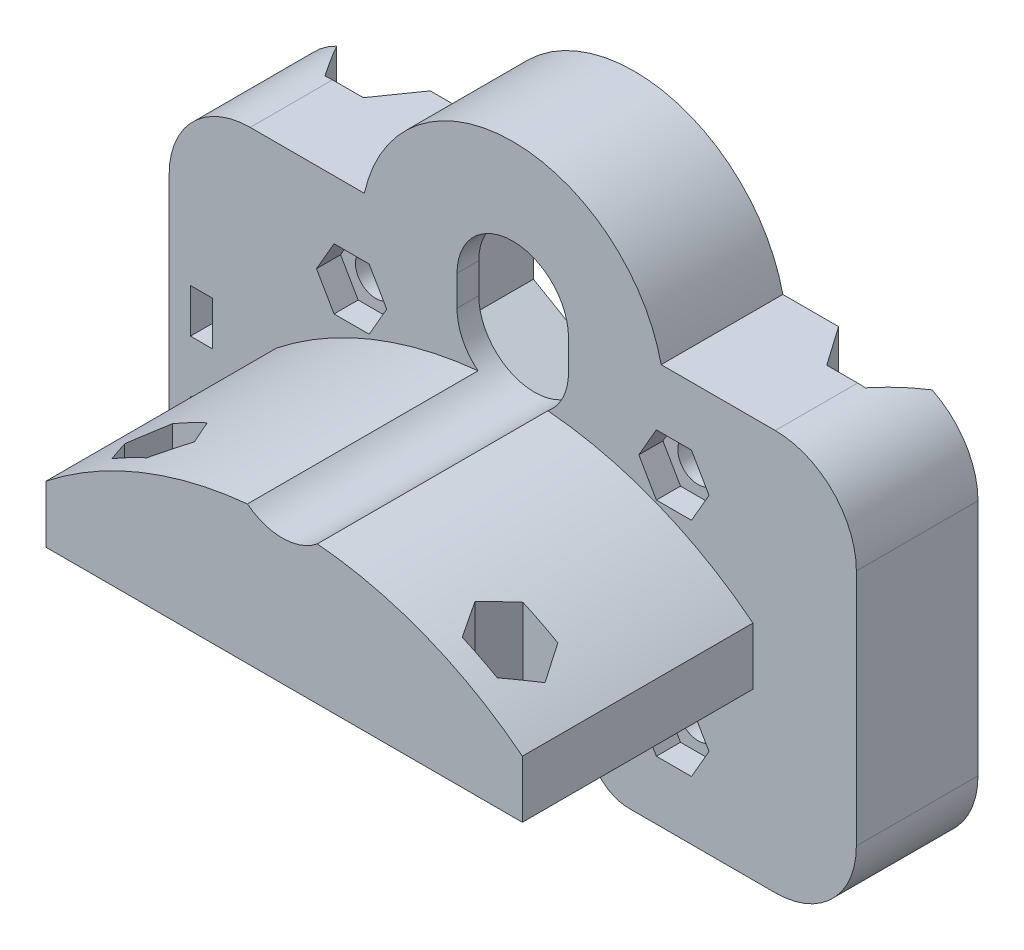
SolidWorks part; units mm, degrees
note: The reader was unsure of these and kept them because the rebuilt part matched: shared geometry of "Sketch11<4>".
material "ABS"
ref_plane "Front Plane" through (0, 0, 0) normal (0, 0, 1) x (1, 0, 0)
ref_plane "Top Plane" through (0, 0, 0) normal (0, 1, 0) x (1, 0, 0)
ref_plane "Right Plane" through (0, 0, 0) normal (1, 0, 0) x (0, 0, -1)
sketch "Sketch1" plane through (0, 0, 0) normal (0, 0, 1) x (1, 0, 0)
  line L0 (0, 41.9085) -> (0, -42.5521) construction
  line L1 (-25.9, -19.75) -> (-11.5, -19.75)
  line L2 (-33.9, -11.75) -> (-33.9, 11.75)
  line L3 (-25.9, 19.75) -> (-14.6437, 19.75)
  line L4 (33.9, -11.75) -> (33.9, 11.75)
  line L5 (-33.9, -19.75) -> (-30.8948, -17.9992) construction
  line L6 (-33.9, 19.75) -> (-28.3215, 16.5) construction
  line L7 (-42.6135, 0) -> (44.2952, 0) construction
  line L8 (7.5, -13) -> (7.5, -15.75)
  line L9 (-7.5, -13) -> (-7.5, -15.75)
  line L10 (11.5, -19.75) -> (25.9, -19.75)
  line L11 (-40.2297, 16.5) -> (44.2952, 16.5) construction
  line L12 (-3.1481, 1.8341) -> (0, 0) construction
  line L13 (28.3215, 16.5) -> (33.9, 19.75) construction
  line L14 (14.6437, 19.75) -> (25.9, 19.75)
  line L15 (0, 0) -> (3.1481, 1.8341) construction
  line L16 (30.8948, -17.9992) -> (33.9, -19.75) construction
  arc A0 (25.9, 19.75) -> (33.9, 11.75) centre (25.9, 11.75) cw
  arc A1 (33.9, -11.75) -> (25.9, -19.75) centre (25.9, -11.75) cw
  arc A2 (-25.9, -19.75) -> (-33.9, -11.75) centre (-25.9, -11.75) cw
  arc A3 (-33.9, 11.75) -> (-25.9, 19.75) centre (-25.9, 11.75) cw
  arc A4 (7.5, -13) -> (-7.5, -13) centre (0, -13) ccw
  arc A5 (-7.5, -15.75) -> (-11.5, -19.75) centre (-11.5, -15.75) cw
  arc A6 (7.5, -15.75) -> (11.5, -19.75) centre (11.5, -15.75) ccw
  circle A7 centre (-15.9, 10.9447) radius 2
  arc A8 (14.6437, 19.75) -> (-14.6437, 19.75) centre (0, 16.5) ccw
  circle A9 centre (-15.9, -10.9447) radius 2
  circle A10 centre (15.9, -10.9447) radius 2
  circle A11 centre (15.9, 10.9447) radius 2
  point P0 (0, 0)
  dimension "D3" = 8
  dimension "D4" = 15
  dimension "D6" = 4
  dimension "D7" = 4
  dimension "D9" = 15
  dimension "D10" = 4
  dimension "D1" = 67.8
  dimension "D2" = 39.5
  dimension "D5" = 6.75
  dimension "D8" = 3.25
  dimension "D11" = 8.8053
  dimension "D12" = 18
extrude "Boss-Extrude4" add sketch "Sketch1" along normal blind 34.75
sketch "Sketch5" plane through (0, 0, 34.75) normal (0, 0, 1) x (1, 0, 0)
  line L0 (-23.3, -3.45) -> (-23.3, 2.2)
  line L1 (23.7, 2.2005) -> (23.7, -3.45)
  line L2 (23.7, -3.45) -> (-23.3, -3.45)
  line L3 (-33.9, 11.75) -> (-33.9, -11.75) construction
  line L4 (-25.9, -19.75) -> (-11.5, -19.75) construction
  arc A0 (-23.3, 2.2) -> (23.7, 2.2005) centre (0.2003, -27.5422) cw
  arc M4 (33.9, 11.75) -> (25.9, 19.75) centre (25.9, 11.75) ccw
  line M5 (25.9, 19.75) -> (14.6437, 19.75)
  arc M6 (14.6437, 19.75) -> (-14.6437, 19.75) centre (0, 16.5) ccw
  line M7 (-14.6437, 19.75) -> (-25.9, 19.75)
  arc M8 (-25.9, 19.75) -> (-33.9, 11.75) centre (-25.9, 11.75) ccw
  line M9 (-33.9, 11.75) -> (-33.9, -11.75)
  arc M10 (-33.9, -11.75) -> (-25.9, -19.75) centre (-25.9, -11.75) ccw
  line M11 (-25.9, -19.75) -> (-11.5, -19.75)
  arc M12 (-11.5, -19.75) -> (-7.5, -15.75) centre (-11.5, -15.75) ccw
  line M13 (-7.5, -15.75) -> (-7.5, -13)
  arc M14 (-7.5, -13) -> (7.5, -13) centre (0, -13) cw
  line M15 (7.5, -13) -> (7.5, -15.75)
  arc M16 (7.5, -15.75) -> (11.5, -19.75) centre (11.5, -15.75) ccw
  line M17 (11.5, -19.75) -> (25.9, -19.75)
  arc M18 (25.9, -19.75) -> (33.9, -11.75) centre (25.9, -11.75) ccw
  line M19 (33.9, -11.75) -> (33.9, 11.75)
  circle M20 centre (-15.9, 10.9447) radius 2
  dimension "D1" = 37.906
  dimension "D2" = 5.65
  dimension "D3" = 47
  dimension "D4" = 5.6505
  dimension "D5" = 10.6
  dimension "D6" = 16.3
extrude "Cut-Extrude2" cut sketch "Sketch5" against normal blind 22.75 contours L0 A0 L1 L2 M19 M4 M5 M6 M7 M8 M9 M10 M11 M12 M13 M14 M15 M16 M17 M18 M20
sketch "Sketch6" plane through (0, 0, 34.75) normal (0, 0, 1) x (1, 0, 0)
  line L0 (-5.5, 14.4931) -> (-5.5, 17.4898)
  line L1 (5.5, 17.4898) -> (5.5, 14.4931)
  line L3 (-23.3, -3.45) -> (-23.3, 2.2) construction
  arc A0 (5.5, 17.4898) -> (-5.5, 17.4898) centre (0, 17.4898) ccw
  arc A1 (-5.5, 14.4931) -> (5.5, 14.4931) centre (0, 14.4931) ccw
  circle A2 centre (0, 16.5) radius 14.9899 construction
  arc A4 (14.6437, 19.75) -> (-14.6437, 19.75) centre (0, 16.5) ccw construction
  dimension "D1" = 0.9898
  dimension "D4" = 5.5
  dimension "D2" = 2.0069
  dimension "D3" = 29.9798
  dimension "D9" = 0.0005
extrude "Cut-Extrude3" cut sketch "Sketch6" against normal up to next
sketch "Sketch7" plane through (0, 0, 12) normal (0, 0, 1) x (1, 0, 0)
  line L0 (0, 35.1713) -> (0, -22.6934) construction
  line L1 (-41.6403, 0) -> (40.1344, 0) construction
sketch "Sketch9" plane through (0, 19.75, 0) normal (0, 1, 0) x (1, 0, 0)
  line L0 (-29.3668, 0) -> (-26.65, -3.88)
  line L1 (-26.65, -3.88) -> (-22.86, -3.88)
  line L2 (-22.86, -3.88) -> (-20.1432, 0)
  line L3 (-20.1432, 0) -> (-29.3668, 0)
  line L4 (-33.9, 0) -> (-33.9, -12) construction
  line L5 (0, 7.9559) -> (0, -40.3734) construction
  line L6 (22.86, -3.88) -> (20.1432, 0)
  line L7 (20.1432, 0) -> (29.3668, 0)
  line L8 (29.3668, 0) -> (26.65, -3.88)
  line L9 (26.65, -3.88) -> (22.86, -3.88)
  line L10 (-14.6437, 0) -> (-25.9, 0) construction
  dimension "D1" = 7.25
  dimension "D2" = 3.79
  dimension "D3" = 3.88
  dimension "D4" = 125
  dimension "D5" = 125
extrude "Cut-Extrude4" cut sketch "Sketch9" against normal through all
sketch "Sketch10" plane through (0, -3.45, 0) normal (0, -1, 0) x (1, 0, 0)
  line L0 (0, 40.7466) -> (0, -14.3002) construction
  line L1 (23.7, 34.75) -> (-23.3, 34.75) construction
  line L2 (-23.3, 12) -> (-23.3, 34.75) construction
  circle A0 centre (-17.3, 29.5) radius 1.8
  circle A1 centre (17.3, 29.5) radius 1.8
  dimension "D1" = 5.25
  dimension "D3" = 3.6
  dimension "D2" = 6
extrude "Cut-Extrude5" cut sketch "Sketch10" against normal up to next
ref_plane "Plane1" through (-0.0486, 10.2061, 0) normal (0.0048, -1, 0) x (-1, -0.0048, 0)
sketch "Sketch11" plane through (-0.0486, 10.2061, 0) normal (0.0048, -1, 0) x (-1, -0.0048, 0)
  line L0 (-23.6833, -34.75) -> (23.3162, -34.75) construction
  line L1 (19.0425, -32.49) -> (20.7688, -29.5)
  line L2 (20.7688, -29.5) -> (19.0425, -26.51)
  line L3 (19.0425, -26.51) -> (15.59, -26.51)
  line L4 (15.59, -26.51) -> (13.8637, -29.5)
  line L5 (13.8637, -29.5) -> (15.59, -32.49)
  line L6 (15.59, -32.49) -> (19.0425, -32.49)
  line L7 (-23.7102, -34.75) -> (-3.5149, -34.75) construction
  line L8 (-19.0096, -26.51) -> (-20.7359, -29.5)
  line L9 (-20.7359, -29.5) -> (-19.0096, -32.49)
  line L10 (-19.0096, -32.49) -> (-15.5571, -32.49)
  line L11 (-15.5571, -32.49) -> (-13.8308, -29.5)
  line L12 (-13.8308, -29.5) -> (-15.5571, -26.51)
  line L13 (-15.5571, -26.51) -> (-19.0096, -26.51)
  circle A0 centre (17.3162, -29.5) radius 2.99 construction
  circle A1 centre (-17.2834, -29.5) radius 2.99 construction
  ellipse E0 centre (17.3162, -29.5) end of major axis (17.3162, -31.3) minor radius 1.8 construction
  ellipse E1 centre (-17.2834, -29.5) end of major axis (-17.2834, -31.3) minor radius 1.8 construction
  ellipse E2 centre (17.3162, -29.5) end of major axis (17.3162, -31.3) minor radius 1.8
  ellipse E3 centre (-17.2834, -29.5) end of major axis (-17.2834, -31.3) minor radius 1.8
  dimension "D1" = 5.98
  dimension "D2" = 5.98
extrude "Cut-Extrude6" cut sketch "Sketch11" along normal offset from surface (11.2319 mm away) 2.35 contours E2 | L5 L6 L1 L2 L3 L4 E2
sketch "Sketch12" plane through (0, -3.45, 0) normal (0, -1, 0) x (-1, 0, 0)
  line L0 (0, 11.1477) -> (0, -60.5065) construction
extrude "Cut-Extrude7" cut sketch "Sketch11<4>" along direction (0, 1, 0) on the side of the normal offset from surface (11.3802 mm away) 2.35 contours E3 | L12 L13 L8 L9 L10 L11 E3
sketch "Sketch11<4>" plane through (-0.0486, 10.2061, 0) normal (0.0048, -1, 0) x (-1, -0.0048, 0) same geometry as "Sketch11"
sketch "Sketch14" plane through (0, 0, 0) normal (0, 0, -1) x (-1, 0, 0)
  line L0 (0, 44.0291) -> (0, -26.022) construction
  line L1 (0, 41.9085) -> (0, -42.5521) construction
  line L3 (0, 3) -> (9.9593, 8.75)
  line L4 (9.9593, 8.75) -> (9.9593, 23.25)
  line L5 (0, 29) -> (9.9593, 23.25)
  line L6 (0, 29) -> (-9.9593, 23.25)
  line L7 (-9.9593, 23.25) -> (-9.9593, 8.75)
  line L8 (-9.9593, 8.75) -> (0, 3)
  line L9 (-20.1432, 19.75) -> (-14.6437, 19.75) construction
  arc A0 (7.5, -13) -> (-7.5, -13) centre (0, -13) ccw construction
  arc A1 (7.5, -13) -> (-7.5, -13) centre (0, -13) ccw
  dimension "D1" = 11.5
  dimension "D2" = 14.5
  dimension "D3" = 60
  dimension "D4" = 11.5
  dimension "D6" = 16.75
extrude "Cut-Extrude8" cut sketch "Sketch14" against normal blind 9.85 contours L0 L6 L7 L8 L3 | L6 L0 L3 L4 L5
sketch "Sketch15" plane through (0, 0, 12) normal (0, 0, 1) x (1, 0, 0)
  line L0 (-14.6437, 19.75) -> (-25.9, 19.75) construction
  line L1 (-14.1679, 13.9447) -> (-17.6321, 13.9447)
  line L2 (-17.6321, 13.9447) -> (-19.3641, 10.9447)
  line L3 (-19.3641, 10.9447) -> (-17.6321, 7.9447)
  line L4 (-17.6321, 7.9447) -> (-14.1679, 7.9447)
  line L5 (-14.1679, 7.9447) -> (-12.4359, 10.9447)
  line L6 (-12.4359, 10.9447) -> (-14.1679, 13.9447)
  line L7 (0, -17.7367) -> (0, 43.9408) construction
  line L8 (-47.3402, 0) -> (50.132, 0) construction
  line L9 (-14.1679, -13.9447) -> (-17.6321, -13.9447)
  line L10 (-12.4359, -10.9447) -> (-14.1679, -13.9447)
  line L11 (-14.1679, -7.9447) -> (-12.4359, -10.9447)
  line L12 (-17.6321, -7.9447) -> (-14.1679, -7.9447)
  line L13 (-19.3641, -10.9447) -> (-17.6321, -7.9447)
  line L14 (-17.6321, -13.9447) -> (-19.3641, -10.9447)
  line L15 (12.4359, -10.9447) -> (14.1679, -13.9447)
  line L16 (14.1679, -7.9447) -> (12.4359, -10.9447)
  line L17 (17.6321, -7.9447) -> (14.1679, -7.9447)
  line L18 (19.3641, -10.9447) -> (17.6321, -7.9447)
  line L19 (17.6321, -13.9447) -> (19.3641, -10.9447)
  line L20 (14.1679, -13.9447) -> (17.6321, -13.9447)
  line L21 (17.6321, 13.9447) -> (19.3641, 10.9447)
  line L22 (19.3641, 10.9447) -> (17.6321, 7.9447)
  line L23 (17.6321, 7.9447) -> (14.1679, 7.9447)
  line L24 (14.1679, 7.9447) -> (12.4359, 10.9447)
  line L25 (12.4359, 10.9447) -> (14.1679, 13.9447)
  line L26 (14.1679, 13.9447) -> (17.6321, 13.9447)
  circle A0 centre (-15.9, 10.9447) radius 3 construction
  circle M26 centre (-15.9, 10.9447) radius 2
  circle M27 centre (15.9, -10.9447) radius 2
  circle M28 centre (15.9, 10.9447) radius 2
  circle M29 centre (-15.9, -10.9447) radius 2
  dimension "D1" = 6
extrude "Cut-Extrude9" cut sketch "Sketch15" against normal blind 2.38 contours M26 | L5 L6 L1 L2 L3 L4 M26 | M28 | L26 L25 L24 L23 L22 L21 M28 | M27 | L15 L20 L19 L18 L17 L16 M27 | M29 | L14 L9 L10 L11 L12 L13 M29
sketch "Sketch16" plane through (-33.9, 0, 0) normal (-1, 0, 0) x (0, 0, 1)
  line L0 (12, -19.75) -> (12, -11.75) construction
  line L1 (3.88, -19.75) -> (0, -19.75) construction
  line L2 (12, -19.75) -> (3.88, -19.75) construction
  line L3 (0, -11.75) -> (0, -18.9598) construction
  line L4 (0, 11.75) -> (0, -11.75) construction
  line L5 (12, -11.75) -> (0, -11.75) construction
  line L6 (12, 11.75) -> (12, -11.75) construction
  line L7 (12, 11.75) -> (0, 11.75) construction
  line L8 (12, 19.75) -> (0, 19.75) construction
  line L9 (12, -19.75) -> (12, -11.75)
  line L10 (3.88, -19.75) -> (0, -19.75)
  line L11 (12, -19.75) -> (3.88, -19.75)
  line L12 (0, -11.75) -> (0, -18.9598)
  line L13 (0, 11.75) -> (0, -11.75)
  line L14 (12, -11.75) -> (0, -11.75)
  line L15 (12, 11.75) -> (12, -11.75)
  line L16 (12, 11.75) -> (0, 11.75)
  line L17 (12, 19.75) -> (0, 19.75)
  circle A0 centre (8.05, -8.33) radius 1.25
  circle A1 centre (8.05, 1.13) radius 1.25
  dimension "D1" = 2.5
  dimension "D3" = 3.95
  dimension "D2" = 11.42
  dimension "D4" = 9.46
  dimension "D5" = 3.95
extrude "Cut-Extrude10" cut sketch "Sketch16" against normal blind 6.1 contours A1 | A0
sketch "Sketch17" plane through (0, 0, 12) normal (0, 0, 1) x (1, 0, 0)
  line L0 (-33.9, 11.75) -> (-33.9, -11.75) construction
  line L1 (-31.8, -1.035) -> (-29.6, -1.035)
  line L2 (-31.8, -1.035) -> (-31.8, 3.295)
  line L3 (-31.8, 3.295) -> (-29.6, 3.295)
  line L4 (-29.6, -1.035) -> (-29.6, 3.295)
  line L5 (-31.8, -6.165) -> (-29.6, -6.165)
  line L6 (-31.8, -6.165) -> (-31.8, -10.495)
  line L7 (-31.8, -10.495) -> (-29.6, -10.495)
  line L8 (-29.6, -6.165) -> (-29.6, -10.495)
  line L9 (-25.9, -19.75) -> (-11.5, -19.75) construction
  dimension "D1" = 2.1
  dimension "D2" = 9.255
  dimension "D3" = 4.33
  dimension "D4" = 2.2
  dimension "D5" = 5.13
  dimension "D6" = 4.33
  dimension "D7" = 2.2
extrude "Cut-Extrude11" cut sketch "Sketch17" against normal blind 6.55
sketch "Sketch18" plane through (-29.6, 0, 0) normal (-1, 0, 0) x (0, 0, 1)
  line L0 (6.7, -1.035) -> (5.45, 1.13)
  line L1 (5.45, -1.035) -> (12, -1.035) construction
  line L2 (5.45, -1.035) -> (5.45, 3.295) construction
  line L3 (5.45, 1.13) -> (6.7, 3.295)
  line L4 (5.45, 3.295) -> (12, 3.295) construction
  line L5 (6.7, 3.295) -> (5.45, 3.295)
  line L6 (5.45, 3.295) -> (5.45, -1.035)
  line L7 (5.45, -1.035) -> (6.7, -1.035)
  line L8 (6.7, -1.035) -> (6.678, -1.0465)
  line L9 (12, 1.13) -> (12, -8.33) construction
  line L10 (12, -1.035) -> (12, 3.295) construction
  line L11 (12, -10.495) -> (12, -6.165) construction
  line L12 (12, -3.6) -> (2.6249, -3.6) construction
  line M3 (12, 3.295) -> (5.45, 3.295)
  line M4 (5.45, 3.295) -> (5.45, -1.035)
  line M5 (5.45, -1.035) -> (12, -1.035)
  dimension "D1" = 120
extrude "Boss-Extrude5" add sketch "Sketch18" along normal blind 2.2 contours L3 M4 M3 | L0 M5 M4
sketch "Sketch21" plane through (-31.8, 0, 0) normal (1, 0, 0) x (0, 0, -1)
  line L0 (-6.7, -6.165) -> (-5.45, -8.33)
  line L1 (-5.45, -6.165) -> (-12, -6.165) construction
  line L2 (-5.45, -6.165) -> (-5.45, -10.495) construction
  line L3 (-5.45, -8.33) -> (-6.7, -10.495)
  line L4 (-5.45, -10.495) -> (-12, -10.495) construction
  line L5 (-6.7, -10.495) -> (-5.45, -10.495)
  line L6 (-5.45, -10.495) -> (-5.45, -6.165)
  line L7 (-5.45, -6.165) -> (-6.7, -6.165)
  line M4 (-12, -10.495) -> (-5.45, -10.495)
  line M5 (-5.45, -10.495) -> (-5.45, -6.165)
  line M6 (-5.45, -6.165) -> (-12, -6.165)
  dimension "D1" = 120
  dimension "D2" = 120
extrude "Boss-Extrude6" add sketch "Sketch21" along normal blind 2.2 contours L0 M6 M5 | L3 M5 M4
